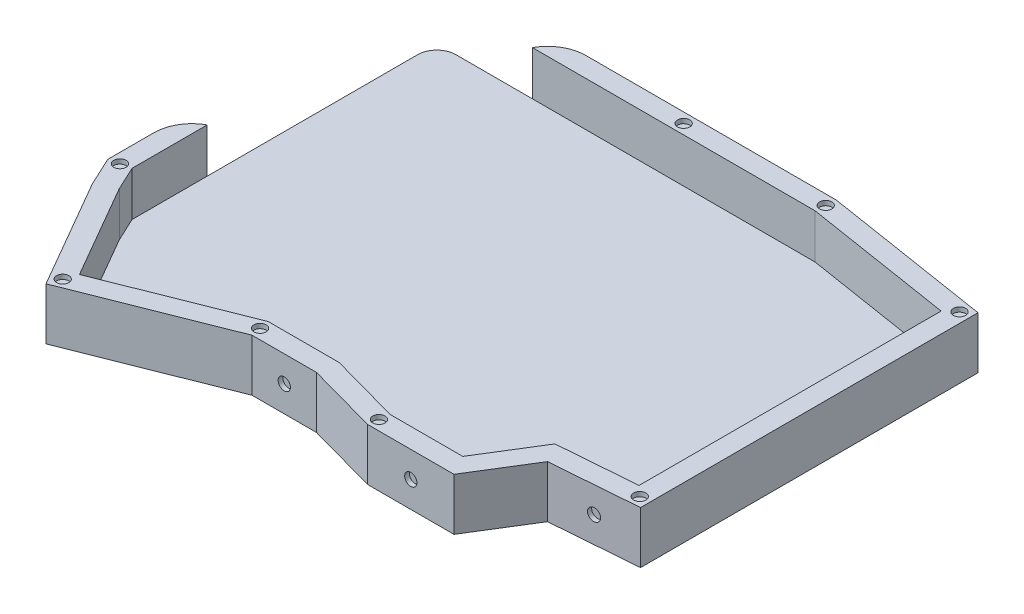
SolidWorks part; units mm, degrees
ref_plane "Front Plane" through (0, 0, 0) normal (0, 0, 1) x (1, 0, 0)
ref_plane "Top Plane" through (0, 0, 0) normal (0, 1, 0) x (1, 0, 0)
ref_plane "Right Plane" through (0, 0, 0) normal (1, 0, 0) x (0, 0, -1)
sketch "Sketch4"
  line L0 (261.3841, 490) -> (1306.7175, 490) construction
sketch "outline" plane through (0, 0, 0) normal (0, 1, 0) x (1, 0, 0)
  line L0 (23.1521, 111.8179) -> (23.1521, 32.6746) construction
  line L1 (23.1521, 32.6746) -> (26.0432, 26.4778) construction
  line L2 (26.0432, 26.4778) -> (40.0838, 2.1711) construction
  line L3 (40.0838, 2.1711) -> (75.1374, 16.0801) construction
  line L4 (75.1374, 16.0801) -> (93.8189, 16.0801) construction
  line L5 (93.8189, 16.0801) -> (112.2703, 10.9819) construction
  line L6 (112.2703, 10.9819) -> (130.9633, 10.9819) construction
  line L7 (130.9633, 10.9819) -> (140.1644, 25.8373) construction
  line L8 (140.1644, 25.8373) -> (160.3881, 27.4157) construction
  line L9 (160.3881, 27.4157) -> (160.3881, 105.6539) construction
  line L10 (160.3881, 105.6539) -> (121.5662, 111.8179) construction
  line L11 (121.5662, 111.8179) -> (23.1521, 111.8179) construction
  line L12 (22.7521, 112.2179) -> (22.7521, 32.5858)
  line L13 (22.7521, 32.5858) -> (25.6881, 26.2928)
  line L14 (25.6881, 26.2928) -> (39.9102, 1.6719)
  line L15 (39.9102, 1.6719) -> (75.2139, 15.6801)
  line L16 (75.2139, 15.6801) -> (93.7646, 15.6801)
  line L17 (93.7646, 15.6801) -> (112.216, 10.5819)
  line L18 (112.216, 10.5819) -> (131.1861, 10.5819)
  line L19 (131.1861, 10.5819) -> (140.3977, 25.4543)
  line L20 (140.3977, 25.4543) -> (160.7881, 27.0457)
  line L21 (160.7881, 27.0457) -> (160.7881, 105.9954)
  line L22 (160.7881, 105.9954) -> (121.5978, 112.2179)
  line L23 (121.5978, 112.2179) -> (22.7521, 112.2179)
  line L36 (23.9521, 111.0179) -> (23.9521, 32.852)
  line L37 (23.9521, 32.852) -> (26.7534, 26.8477)
  line L38 (26.7534, 26.8477) -> (40.431, 3.1695)
  line L39 (40.431, 3.1695) -> (74.9845, 16.8801)
  line L40 (74.9845, 16.8801) -> (93.9274, 16.8801)
  line L41 (93.9274, 16.8801) -> (112.3788, 11.7819)
  line L42 (112.3788, 11.7819) -> (130.5178, 11.7819)
  line L43 (130.5178, 11.7819) -> (139.6978, 26.6033)
  line L44 (139.6978, 26.6033) -> (159.5881, 28.1556)
  line L45 (159.5881, 28.1556) -> (159.5881, 104.9709)
  line L46 (159.5881, 104.9709) -> (121.5031, 111.0179)
  line L47 (121.5031, 111.0179) -> (23.9521, 111.0179)
  line L48 (17.5521, 117.4179) -> (17.5521, 31.4325)
  line L49 (17.5521, 31.4325) -> (21.0718, 23.8885)
  line L50 (21.0718, 23.8885) -> (37.6538, -4.8178)
  line L51 (37.6538, -4.8178) -> (76.2079, 10.4801)
  line L52 (76.2079, 10.4801) -> (93.0594, 10.4801)
  line L53 (93.0594, 10.4801) -> (111.5108, 5.3819)
  line L54 (111.5108, 5.3819) -> (134.0819, 5.3819)
  line L55 (134.0819, 5.3819) -> (143.4304, 20.4752)
  line L56 (143.4304, 20.4752) -> (165.9881, 22.2357)
  line L57 (165.9881, 22.2357) -> (165.9881, 110.4349)
  line L58 (165.9881, 110.4349) -> (122.008, 117.4179)
  line L59 (122.008, 117.4179) -> (17.5521, 117.4179)
  dimension "D1" = 137.236
  dimension "D3" = 5.2
  dimension "D4" = 1.2
  dimension "D2" = 0.4
sketch "cutout" plane through (0, 0, 0) normal (0, 1, 0) x (1, 0, 0)
  line L0 (47.7521, 112.2179) -> (47.7521, 117.4179)
  line L1 (22.7521, 112.2179) -> (47.7521, 112.2179)
  line L2 (22.7521, 112.2179) -> (22.7521, 52.2179)
  line L3 (22.7521, 52.2179) -> (47.7521, 52.2179)
  line L4 (47.7521, 112.2179) -> (47.7521, 52.2179)
  line L5 (122.008, 117.4179) -> (17.5521, 117.4179) construction
  line L6 (47.7521, 117.4179) -> (17.5521, 117.4179)
  line L7 (17.5521, 117.4179) -> (17.5521, 52.2179)
  line L8 (17.5521, 117.4179) -> (17.5521, 31.4325) construction
  line L9 (17.5521, 52.2179) -> (22.7521, 52.2179)
  dimension "D1" = 25
  dimension "D2" = 60
extrude "Boss-Extrude1" add sketch "outline" along normal blind 2 contours L12 L13 L14 L15 L16 L17 L18 L19 L20 L21 L22 L23
extrude "Boss-Extrude2" add sketch "outline<7>" along normal blind 13.6 contours L58 L59 L48 L49 L50 L51 L52 L53 L54 L55 L56 L57 L23 L22 L21 L20 L19 L18 L17 L16 L15 L14 L13 L12 region at (69.7801, 0, -115.495)
sketch "outline<7>" plane through (0, 0, 0) normal (0, 1, 0) x (1, 0, 0) same geometry as "outline"
extrude "Cut-Extrude1" cut sketch "cutout" along normal through all contours L7 L9 L2 L1 L0 L6 region at (35.2521, 0, -112.9365)
sketch "Sketch5" plane through (0, 13.6, 0) normal (0, 1, 0) x (1, 0, 0)
  line L0 (17.5521, 31.4325) -> (22.7521, 32.5858) construction
  line L1 (22.7521, 32.5858) -> (37.6538, -4.8178) construction
  line L2 (37.6538, -4.8178) -> (39.9102, 1.6719) construction
  line L3 (39.9102, 1.6719) -> (76.2079, 10.4801) construction
  line L4 (76.2079, 10.4801) -> (75.2139, 15.6801) construction
  line L5 (75.2139, 15.6801) -> (93.0594, 10.4801) construction
  line L6 (93.0594, 10.4801) -> (93.7646, 15.6801) construction
  line L7 (93.7646, 15.6801) -> (111.5108, 5.3819) construction
  line L8 (111.5108, 5.3819) -> (112.216, 10.5819) construction
  line L9 (112.216, 10.5819) -> (134.0819, 5.3819) construction
  line L10 (134.0819, 5.3819) -> (131.1861, 10.5819) construction
  line L11 (131.1861, 10.5819) -> (143.4304, 20.4752) construction
  line L12 (143.4304, 20.4752) -> (140.3977, 25.4543) construction
  line L13 (140.3977, 25.4543) -> (165.9881, 22.2357) construction
  line L14 (165.9881, 22.2357) -> (160.7881, 27.0457) construction
  line L15 (160.7881, 27.0457) -> (165.9881, 110.4349) construction
  line L16 (165.9881, 110.4349) -> (160.7881, 105.9954) construction
  line L17 (160.7881, 105.9954) -> (122.008, 117.4179) construction
  line L18 (122.008, 117.4179) -> (121.5978, 112.2179) construction
  line L19 (121.5978, 112.2179) -> (47.7521, 117.4179) construction
  point P43 (20.1521, 32.0091)
  point P45 (38.782, -1.573)
  point P47 (75.7109, 13.0801)
  point P49 (111.8634, 7.9819)
  point P51 (163.3881, 24.6407)
  point P53 (163.3881, 108.2151)
  point P55 (121.8029, 114.8179)
  point P57 (84.6749, 114.8179)
hole_wizard "top holes" positions "Sketch5" profile "Sketch10" hole size "Ø3.0" standard "ANSI Metric"
sketch "Sketch10" plane through (84.6749, 13.6, -114.8179) normal (1, 0, 0) x (0, 0, 1)
  line L0 (0, 0) -> (0, 1.2)
  line L1 (0, 1.2) -> (1.6, 1.2)
  line L2 (1.6, 1.2) -> (1.6, 0)
  line L5 (1.6, 0) -> (0, 0)
  line L10 (0, 1.2) -> (-1.6, 1.2) construction
  line L11 (0, -6.35) -> (0, 107.95) construction
  dimension "Hole Dia." = 3.2
  dimension "Hole Depth" = 1.2
  dimension "Drill Angle" = 180
sketch "Sketch11" plane through (0, 0, -10.4801) normal (0, 0, 1) x (1, 0, 0)
  line L0 (76.2079, 0) -> (93.0594, 13.6) construction
  point P6 (84.6336, 6.8)
sketch "Sketch12" plane through (0, 0, -5.3819) normal (0, 0, 1) x (1, 0, 0)
  line L0 (111.5108, 0) -> (134.0819, 13.6) construction
  point P6 (122.7964, 6.8)
sketch "Sketch13" plane through (-0.72, 0, -9.2249) normal (0.0778, 0, 0.997) x (0.997, 0, -0.0778)
  line L0 (144.5887, 0) -> (167.215, 13.6) construction
  point P6 (155.9018, 6.8)
hole_wizard "wrist 1" positions "Sketch11" profile "Sketch14" hole size "Ø3.0" standard "ANSI Metric"
sketch "Sketch14" plane through (84.6336, 6.8, -10.4801) normal (1, 0, 0) x (0, -1, 0)
  line L0 (0, 0) -> (0, 1.2)
  line L1 (0, 1.2) -> (1.6, 1.2)
  line L2 (1.6, 1.2) -> (1.6, 0)
  line L5 (1.6, 0) -> (0, 0)
  line L10 (0, 1.2) -> (-1.6, 1.2) construction
  line L11 (0, -6.35) -> (0, 107.95) construction
  dimension "Hole Dia." = 3.2
  dimension "Hole Depth" = 1.2
  dimension "Drill Angle" = 180
hole_wizard "wrist 2" positions "Sketch12" profile "Sketch15" hole size "Ø3.0" standard "ANSI Metric"
sketch "Sketch15" plane through (122.7964, 6.8, -5.3819) normal (1, 0, 0) x (0, -1, 0)
  line L0 (0, 0) -> (0, 1.2)
  line L1 (0, 1.2) -> (1.6, 1.2)
  line L2 (1.6, 1.2) -> (1.6, 0)
  line L5 (1.6, 0) -> (0, 0)
  line L10 (0, 1.2) -> (-1.6, 1.2) construction
  line L11 (0, -6.35) -> (0, 107.95) construction
  dimension "Hole Dia." = 3.2
  dimension "Hole Depth" = 1.2
  dimension "Drill Angle" = 180
hole_wizard "wrist 3" positions "Sketch13" profile "Sketch16" hole size "Ø3.0" standard "ANSI Metric"
sketch "Sketch16" plane through (154.7092, 6.8, -21.3554) normal (0, 1, 0) x (0.997, 0, -0.0778)
  line L0 (0, 0) -> (0, 1.2)
  line L1 (0, 1.2) -> (1.6, 1.2)
  line L2 (1.6, 1.2) -> (1.6, 0)
  line L5 (1.6, 0) -> (0, 0)
  line L10 (0, 1.2) -> (-1.6, 1.2) construction
  line L11 (0, -6.35) -> (0, 107.95) construction
  dimension "Hole Dia." = 3.2
  dimension "Hole Depth" = 1.2
  dimension "Drill Angle" = 180
fillet "Fillet1" radius 5 1 edges at (22.7521, 1, -112.2179)
fillet "Fillet2" radius 10 1 edges at (47.7521, 6.8, -117.4179)
fillet "Fillet3" radius 10 1 edges at (17.5521, 6.8, -52.2179)
mirror "Mirror1" [suppressed] of bodies 132
delete or keep bodies "Body-Delete/Keep 1" [suppressed] type delete bodies bodies 132
